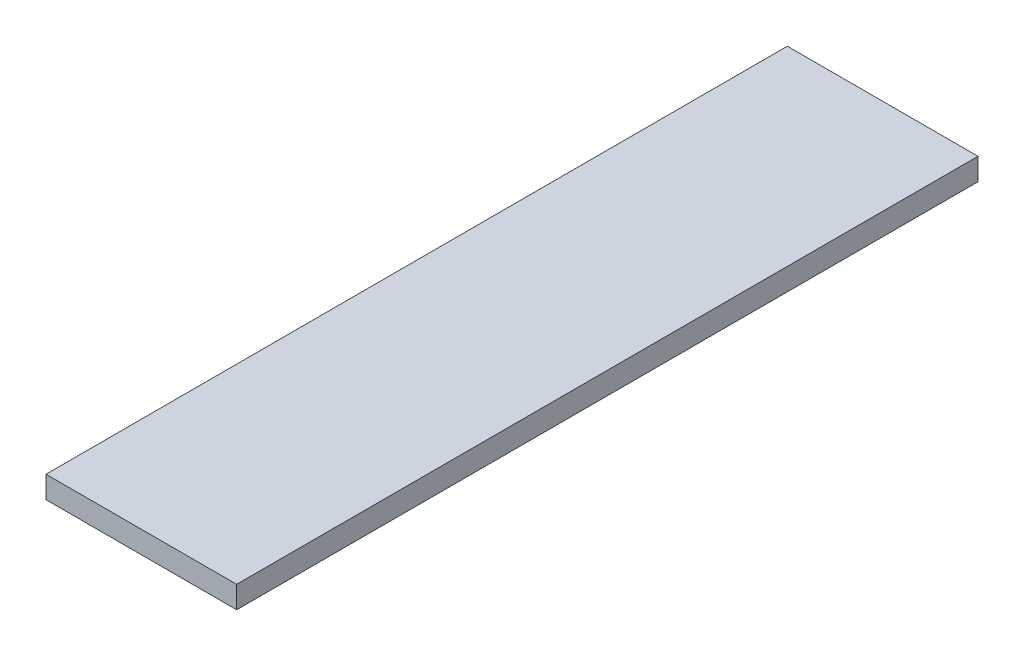
SolidWorks part; units mm, degrees
ref_plane "Front Plane" through (0, 0, 0) normal (0, 0, 1) x (1, 0, 0)
ref_plane "Top Plane" through (0, 0, 0) normal (0, 1, 0) x (1, 0, 0)
ref_plane "Right Plane" through (0, 0, 0) normal (1, 0, 0) x (0, 0, -1)
sketch "Sketch1" plane through (0, 0, 0) normal (0, 0, 1) x (1, 0, 0)
  line L7 (-30.861, -3.5719) -> (30.861, -3.5719)
  line L8 (-30.861, -3.5719) -> (-30.861, 3.5719)
  line L9 (-30.861, 3.5719) -> (30.861, 3.5719)
  line L10 (30.861, -3.5719) -> (30.861, 3.5719)
  line L11 (-30.861, -3.5719) -> (30.861, 3.5719) construction
  line L12 (-30.861, 3.5719) -> (30.861, -3.5719) construction
  point P4 (0, 0)
  point P14 (0, 0)
  dimension "Width" = 61.722
  dimension "Thickness" = 7.1437
sketch "Sketch2" plane through (0, 0, 0) normal (0, 1, 0) x (0, 0, -1)
  line L0 (120, 30.861) -> (-120, 30.861) construction
  point P0 (-42.8475, 30.861)
  point P4 (0, 30.861)
  point P6 (42.8475, 30.861)
  dimension "Length" = 240
  dimension "D1" = 77.1525
  dimension "D2" = 77.1525
sketch "Sketch3" plane through (0, 0, 0) normal (0, 0, 1) x (1, 0, 0)
  line L6 (-30.861, 3.5719) -> (30.861, 3.5719)
  line L7 (30.861, 3.5719) -> (30.861, -3.5719)
  line L8 (30.861, -3.5719) -> (-30.861, -3.5719)
  line L9 (-30.861, -3.5719) -> (-30.861, 3.5719)
extrude "Boss-Extrude1" add sketch "Sketch3" along normal mid plane 240
equation "\"D1@Boss-Extrude1\" = \"Length@Sketch2\""
equation "\"D1@Sketch2\"=\"Width@Sketch1\" * 1.25"
equation "\"D2@Sketch2\"=\"D1@Sketch2\""
